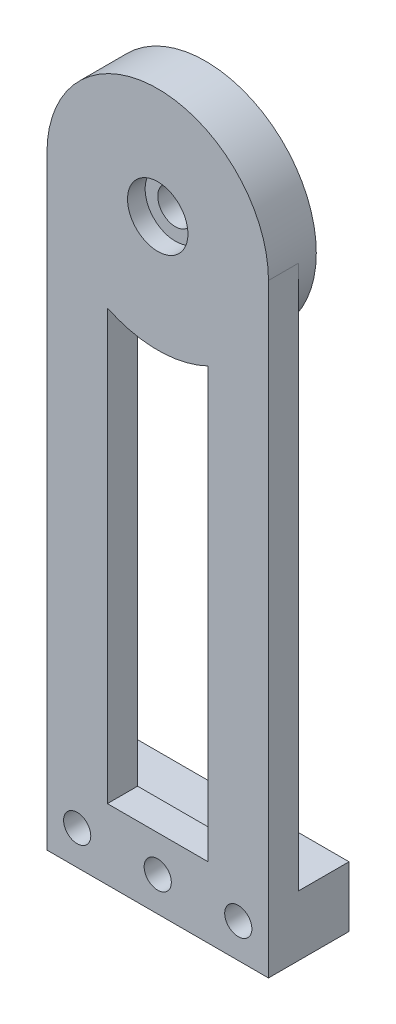
SolidWorks part; units mm, degrees
ref_plane "Front Plane" through (0, 0, 0) normal (0, 0, 1) x (1, 0, 0)
ref_plane "Top Plane" through (0, 0, 0) normal (0, 1, 0) x (1, 0, 0)
ref_plane "Right Plane" through (0, 0, 0) normal (1, 0, 0) x (0, 0, -1)
sketch "Sketch1" plane through (0, 0, 0) normal (0, 0, 1) x (1, 0, 0)
  line L0 (0, 30) -> (0, -30) construction
  line L1 (-11, 30) -> (-11, -30)
  line L2 (11, 30) -> (11, -30)
  line L3 (-11, -30) -> (11, -30)
  line L5 (-11, -30) -> (11, -30)
  line L6 (-11, -30) -> (-11, -24)
  line L7 (-11, -24) -> (11, -24)
  line L8 (11, -30) -> (11, -24)
  line L10 (-5, 19.6438) -> (-5, -23)
  line L11 (-5, -23) -> (5, -23)
  line L12 (5, 19.6438) -> (5, -23)
  circle A0 centre (0, 30) radius 11
  arc A2 (-5, 19.6438) -> (5, 19.6438) centre (0, 30) ccw
  point P8 (0, 0)
  point P16 (0, 0)
  dimension "D2" = 22
  dimension "D6" = 6
  dimension "D7" = 11.5
  dimension "D1" = 60
  dimension "D3" = 6
  dimension "D4" = 1
  dimension "D5" = 6
extrude "Boss-Extrude1" add sketch "Sketch1" along normal blind 3 contours A0 | L0 A0 L1 | A0 L0 L2 | L6 L5 L8 L7 region at (0, 18.9417, 0) region at (0, 30, 0)
extrude "Boss-Extrude2" add sketch "Sketch1<3>" against normal blind 1.75 contours A0 region at (0, 30, 0)
sketch "Sketch1<3>" plane through (0, 0, 0) normal (0, 0, 1) x (1, 0, 0) same geometry as "Sketch1"
sketch "Sketch2" plane through (0, 0, 3) normal (0, 0, 1) x (1, 0, 0)
  circle A0 centre (0, 30) radius 1.75
  circle A3 centre (0, 30) radius 3
  dimension "D1" = 3.5
  dimension "D2" = 6
extrude "Cut-Extrude1" cut sketch "Sketch2" against normal up to surface (4.75 mm away) contours A0 region at (0, 30, 3) up to face at (11, 30, -1.75)
extrude "Cut-Extrude2" cut sketch "Sketch2<3>" against normal offset from surface (1.75 mm away) 3 contours A3 A0 region at (-2.9151, 30, 3) up to face at (1.75, 30, -1.75)
sketch "Sketch2<3>" plane through (0, 0, 3) normal (0, 0, 1) x (1, 0, 0) same geometry as "Sketch2"
extrude "Boss-Extrude3" add sketch "Sketch1<6>" against normal blind 5 contours L7 L0 L5 L2 | L0 L7 L1 L3 region at (-5.5, -27, 0) region at (5.5, -27, 0)
sketch "Sketch1<6>" plane through (0, 0, 0) normal (0, 0, 1) x (1, 0, 0) same geometry as "Sketch1"
sketch "Sketch3" plane through (0, 0, 3) normal (0, 0, 1) x (1, 0, 0)
  line L0 (-11, -30) -> (11, -30) construction
  circle A0 centre (0, -26.6) radius 1.35
  dimension "D2" = 2.7
  dimension "D1" = 3.4
extrude "Cut-Extrude3" cut sketch "Sketch3" against normal up to surface (8 mm away) up to face at (0, -27, -5)
pattern_linear "LPattern1" count 2 spacing 8 along (1, 0, 0) count 2 spacing 8 along (-1, 0, 0) of "Cut-Extrude3"
